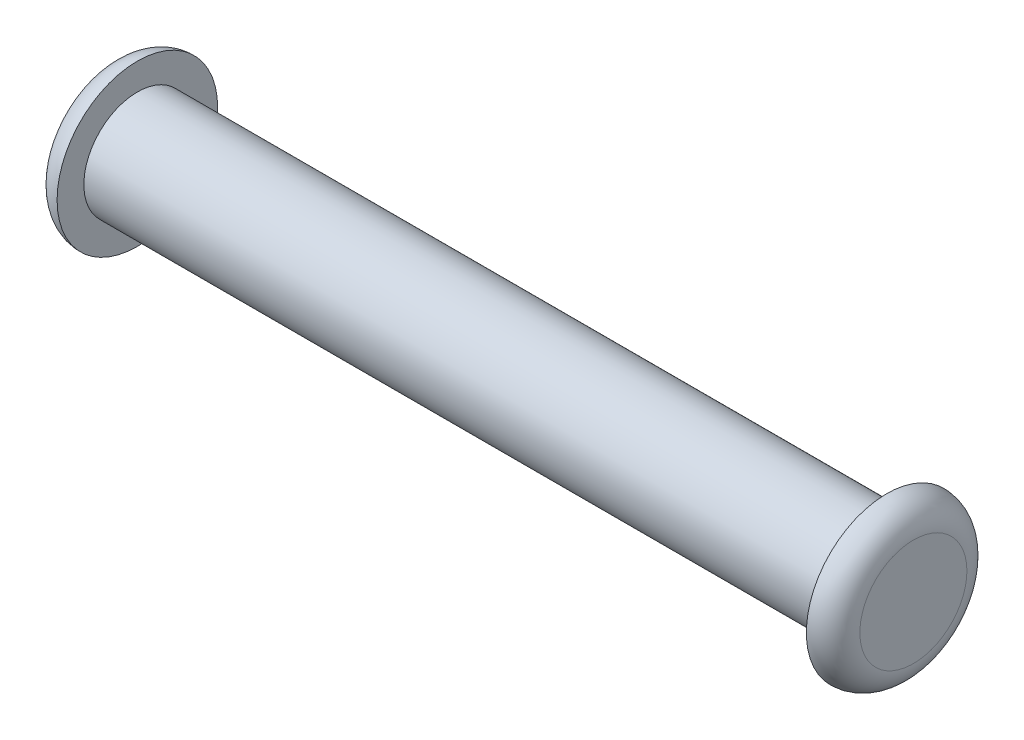
SolidWorks part; units mm, degrees
material "Ti-6Al-4VSolution treated and aged (SS)"
ref_plane "Front Plane" through (0, 0, 0) normal (0, 0, 1) x (1, 0, 0)
ref_plane "Top Plane" through (0, 0, 0) normal (0, 1, 0) x (1, 0, 0)
ref_plane "Right Plane" through (0, 0, 0) normal (1, 0, 0) x (0, 0, -1)
sketch "Sketch2" plane through (0, 0, 0) normal (1, 0, 0) x (0, 0, -1)
  circle A0 centre (0, 0) radius 2
  dimension "D1" = 4
extrude "Boss-Extrude1" add sketch "Sketch2" along normal blind 28
ref_plane "MiddlePlane1" through (14, 0, 0) normal (-1, 0, 0) x (0, 0, 1)
sketch "Sketch3" plane through (28, 0, 0) normal (1, 0, 0) x (0, 0, -1)
  circle A0 centre (0, 0) radius 3
  dimension "D1" = 6
extrude "Boss-Extrude2" add sketch "Sketch3" along normal blind 1
fillet "Fillet1" radius 1 1 edges at (29, 0, -3)
mirror "Mirror1" about plane through (14, 0, 0) normal (-1, 0, 0) of "Fillet1", "Boss-Extrude2"
